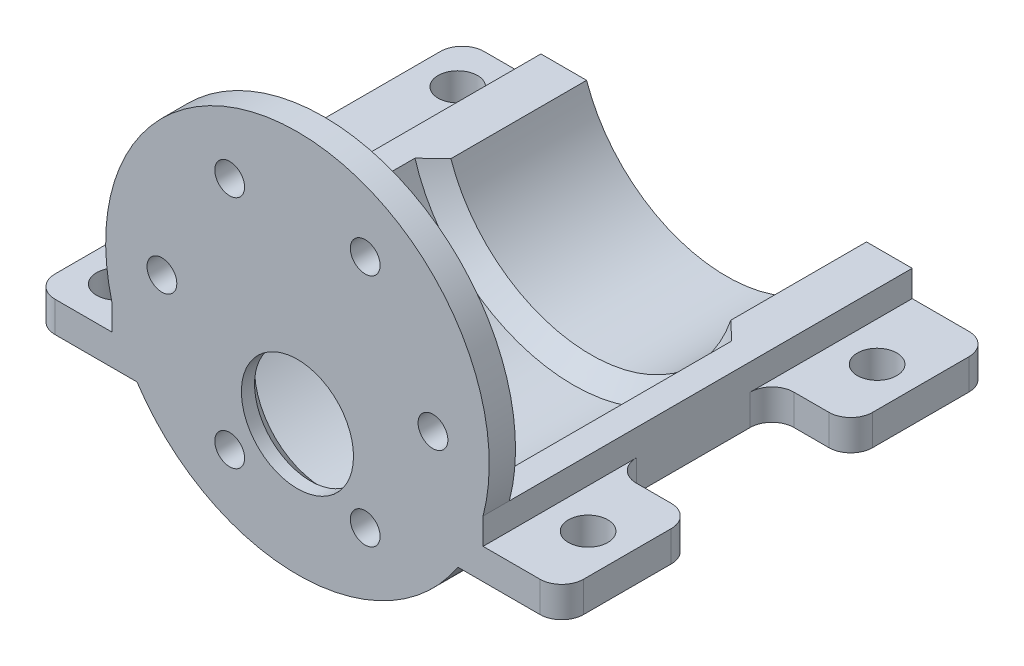
SolidWorks part; units mm, degrees
ref_plane "Front Plane" through (0, 0, 0) normal (0, 0, 1) x (1, 0, 0)
ref_plane "Top Plane" through (0, 0, 0) normal (0, 1, 0) x (1, 0, 0)
ref_plane "Right Plane" through (0, 0, 0) normal (1, 0, 0) x (0, 0, -1)
sketch "Sketch1" plane through (0, 0, 0) normal (0, 0, 1) x (1, 0, 0)
  line L0 (0, 0) -> (15.475, 0) construction
  line L1 (0, 0) -> (15.475, 0) construction
  line L2 (0, 0) -> (7.7375, -13.4017) construction
  line L3 (20.1832, -8.5) -> (30.1832, -8.5)
  line L4 (0, 0) -> (0, -7) construction
  line L5 (30.1832, -8.5) -> (30.1832, -12)
  line L6 (-20.1832, -8.5) -> (20.1832, -8.5)
  line L7 (30.1832, -12) -> (18.3197, -12)
  line L8 (-20.1832, -8.5) -> (-30.1832, -8.5)
  line L9 (-30.1832, -8.5) -> (-30.1832, -12)
  line L10 (-30.1832, -12) -> (-18.3197, -12)
  line L11 (-21.1981, -8.5) -> (-21.1981, -5.5)
  line L12 (-21.1981, -5.5) -> (-15.98, -5.5)
  line L13 (21.1981, -8.5) -> (21.1981, -5.5)
  line L14 (21.1981, -5.5) -> (15.98, -5.5)
  circle A0 centre (0, 0) radius 18.9
  circle A2 centre (0, 0) radius 16.9
  circle A4 centre (15.475, 0) radius 1.7
  circle A5 centre (7.7375, -13.4017) radius 1.7
  circle A6 centre (-7.7375, -13.4017) radius 1.7
  circle A7 centre (-15.475, 0) radius 1.7
  circle A8 centre (-7.7375, 13.4017) radius 1.7
  circle A9 centre (7.7375, 13.4017) radius 1.7
  circle A10 centre (0, 0) radius 21.9
  circle A11 centre (0, 0) radius 18.15
  circle A22 centre (0, -7) radius 6.4
  dimension "D1" = 37.8
  dimension "D2" = 33.8
  dimension "D3" = 3.4
  dimension "D7" = 43.8
  dimension "D8" = 36.3
  dimension "D12" = 12.8
  dimension "D4" = 6
  dimension "D5" = 60
  dimension "D6" = 15.475
  dimension "D13" = 1.5
  dimension "D14" = 7
  dimension "D16" = 3.5
  dimension "D17" = 10
  dimension "D18" = 3
extrude "Boss-Extrude1" add sketch "Sketch1" against normal blind 3 from offset 94 contours L6 A10 A0 | A11 L6 A0 | L6 A11 A2 A5 A6 | A22 L6 A2 A6 A5 | A22 L6 A2 A4 A9 A8 A7 | L12 A11 L6 A2 | A11 L12 A0 L6 | L12 A10 L6 A0 | L14 A10 L12 A0 | A11 L14 A0 L12 | L14 A11 L12 A2 A7 A8 A9 A4 | L6 A10 L14 A0 | A11 L6 A0 L14 | L6 A11 L14 A2 region at (18.9554, -10.0924, 0) region at (19.1257, -7.0145, 0) region at (0, -18.5467, 0) region at (17.1179, -7.018, 0) region at (19.6401, -4.9834, 0) region at (0, -17.8151, 0) region at (16.027, -7.0205, 0) region at (-17.1179, -7.018, 0) region at (-19.1257, -7.0145, 0) region at (17.6893, -5.0501, 0) region at (12.0472, -11.4146, 0) region at (0, 3.7482, 0) region at (-16.027, -7.0205, 0) region at (16.6383, -5.0668, 0)
extrude "Boss-Extrude2" add sketch "Sketch1<5>" against normal blind 27.5 from surface contours L6 A10 A0 | L12 A10 L6 A0 | L6 A10 L14 A0 region at (18.9554, -10.0924, 0) region at (19.1257, -7.0145, 0) region at (-19.1257, -7.0145, 0) starting at face at (-13.775, 0, 91)
sketch "Sketch1<5>" plane through (0, 0, 0) normal (0, 0, 1) x (1, 0, 0) same geometry as "Sketch1"
extrude "Boss-Extrude3" add sketch "Sketch1<6>" against normal blind 18.5 from surface contours L6 A10 A0 | A11 L6 A0 | L6 A11 A2 A5 A6 | A2 A6 | A2 A5 | L12 A10 L6 A0 | A11 L12 A0 L6 | L12 A11 L6 A2 | L6 A11 L14 A2 | A11 L6 A0 L14 | L6 A10 L14 A0 region at (18.9554, -10.0924, 0) region at (19.1257, -7.0145, 0) region at (0, -18.5467, 0) region at (17.1179, -7.018, 0) region at (0, -17.8151, 0) region at (16.027, -7.0205, 0) region at (-17.1179, -7.018, 0) region at (-19.1257, -7.0145, 0) region at (-16.027, -7.0205, 0) region at (8.5026, -14.727, 0) region at (-8.5026, -14.727, 0) starting at face at (0, -12.95, 63.5)
sketch "Sketch1<6>" plane through (0, 0, 0) normal (0, 0, 1) x (1, 0, 0) same geometry as "Sketch1"
extrude "Boss-Extrude7" add sketch "Sketch1<11>" along normal up to surface (94 mm away) from surface contours A10 L8 L9 L10 | A10 L8 | A10 L7 L5 L3 | A10 L3 L13 region at (20.8725, -7.5426, 0) region at (24.738, -10.2999, 0) region at (-24.738, -10.2999, 0) region at (-20.8725, -7.5426, 0) up to face at (-13.775, 0, 94) starting at face at (0, -12.45, 45)
sketch "Sketch1<11>" plane through (0, 0, 0) normal (0, 0, 1) x (1, 0, 0) same geometry as "Sketch1"
sketch "Sketch4" plane through (0, -8.5, 0) normal (0, 1, 0) x (1, 0, 0)
  line L0 (30.1832, -94) -> (30.1832, -45) construction
  line L5 (-25.6906, -50) -> (-25.6906, -89) construction
  line L6 (-30.1832, -94) -> (-30.1832, -45) construction
  line L7 (-30.1832, -45) -> (-21.1981, -45) construction
  line L9 (-25.6906, -50) -> (-25.6906, -45) construction
  line L10 (-25.6906, -89) -> (-25.6906, -94) construction
  line L11 (-30.1832, -94) -> (-21.1981, -94) construction
  line L13 (30.1832, -79) -> (21.1981, -79)
  line L14 (30.1832, -79) -> (30.1832, -61)
  line L15 (30.1832, -61) -> (21.1981, -61)
  line L16 (21.1981, -79) -> (21.1981, -61)
  line L17 (30.1832, -79) -> (21.1981, -61) construction
  line L18 (30.1832, -61) -> (21.1981, -79) construction
  line L23 (25.6906, -45) -> (25.6906, -61) construction
  line L24 (30.1832, -45) -> (21.1981, -45) construction
  line L25 (25.6906, -79) -> (25.6906, -94) construction
  line L26 (30.1832, -94) -> (21.1981, -94) construction
  circle A0 centre (-25.6906, -50) radius 2.25
  circle A1 centre (-25.6906, -89) radius 2.25
  circle A4 centre (25.6906, -86.5) radius 2.25
  circle A5 centre (25.6906, -53.5) radius 2.25
  point P8 (-25.6906, -69.5)
  point P11 (-30.1832, -69.5)
  point P15 (-25.6906, -45)
  point P25 (25.6906, -70)
  point P35 (25.6906, -86.5)
  point P37 (0, 0)
  point P38 (25.6906, -54.4924)
  point P39 (0, 0)
  dimension "D1" = 4.5
  dimension "D4" = 8.5
  dimension "D2" = 5
  dimension "D3" = 7.5
  dimension "D5" = 7.5
extrude "Cut-Extrude5" cut sketch "Sketch4" against normal through all both and the other way through all contours A0 | A1 | A4 | L16 L13 L14 L15 | A5 region at (25.6906, -8.5, 70) region at (-25.6906, -8.5, 50) region at (-25.6906, -8.5, 89) region at (25.6906, -8.5, 86.5)
chamfer "Chamfer3" distance 3 angle 45 1 edges at (0, -16.9, 63.5)
chamfer "Chamfer4" distance 1.5 angle 45 1 edges at (6.4, -7, 91)
fillet "Fillet2" radius 2.5 8 edges at (-30.1832, -10.25, 94) (30.1832, -10.25, 94) (-30.1832, -10.25, 45) (30.1832, -10.25, 45) (30.1832, -10.25, 79) (21.1981, -10.25, 79) (30.1832, -10.25, 61) (21.1981, -10.25, 61)
